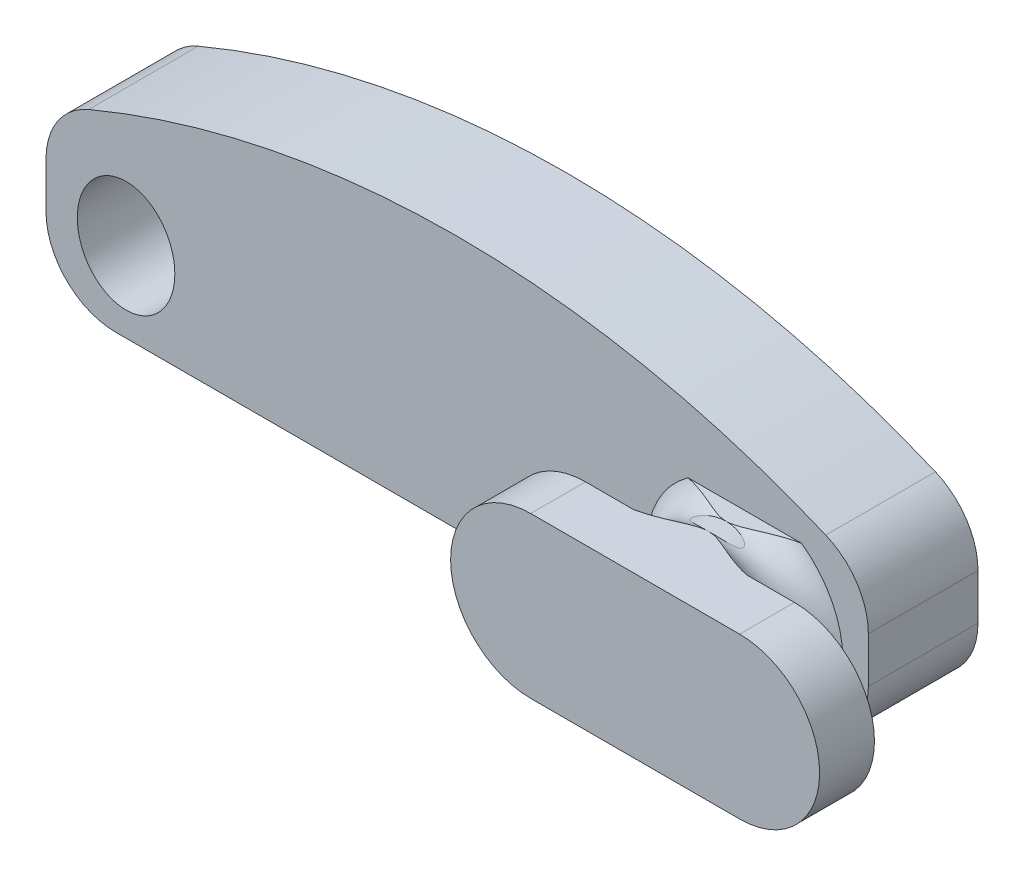
SolidWorks part; units mm, degrees
ref_plane "Front Plane" through (0, 0, 0) normal (0, 0, 1) x (1, 0, 0)
ref_plane "Top Plane" through (0, 0, 0) normal (0, 1, 0) x (1, 0, 0)
ref_plane "Right Plane" through (0, 0, 0) normal (1, 0, 0) x (0, 0, -1)
sketch "Sketch1" plane through (0, 0, 0) normal (0, 0, 1) x (1, 0, 0)
  line L1 (0, 0) -> (-30, 0)
  line L2 (0, 0) -> (0, 5.842)
  line L3 (0, 5.842) -> (-30, 5.842)
  line L4 (-30, 0) -> (-30, 5.842)
  dimension "D1" = 30
  dimension "D2" = 5.842
extrude "Boss-Extrude1" add sketch "Sketch1" along normal blind 4
sketch "Sketch2" plane through (0, 0, 4) normal (0, 0, 1) x (1, 0, 0)
  line L0 (-30, 2.921) -> (0, 2.921) construction
  line L1 (-30, 5.842) -> (-30, 0) construction
  line L2 (0, 0) -> (0, 5.842) construction
  line L3 (-30, 0) -> (0, 0) construction
  line L4 (-1.5875, 5.842) -> (-7.4295, 5.842)
  line L5 (-1.5875, 5.842) -> (-1.5875, 0)
  line L6 (-1.5875, 0) -> (-7.4295, 0)
  line L7 (-7.4295, 5.842) -> (-7.4295, 0)
  line L9 (0, 5.842) -> (-30, 5.842) construction
  ellipse E0 centre (-4.5085, 2.921) end of major axis (-4.5085, 0) minor radius 2.54
  dimension "D1" = 5.08
  dimension "D3" = 1.5875
extrude "Boss-Extrude2" add sketch "Sketch2" along normal blind 2 contours E0
sketch "Sketch3" plane through (0, 0, 6) normal (0, 0, 1) x (1, 0, 0)
  line L0 (-0.6985, 2.921) -> (-8.3185, 2.921) construction
  line L1 (-0.6985, 0) -> (-8.3185, 0)
  line L2 (-0.6985, 5.842) -> (-8.3185, 5.842)
  line L3 (-7.0485, 2.921) -> (-1.9685, 2.921) construction
  line L4 (-4.5085, 5.842) -> (-4.5085, 0) construction
  line L5 (-4.5085, 5.842) -> (-30, 5.842) construction
  arc A1 (-0.6985, 0) -> (-0.6985, 5.842) centre (-0.6985, 2.921) ccw
  arc A2 (-8.3185, 5.842) -> (-8.3185, 0) centre (-8.3185, 2.921) ccw
  ellipse E3 centre (-4.5085, 2.921) end of major axis (-4.5085, 0) minor radius 2.54 construction
  point P2 (-4.5085, 2.921)
  point P28 (-4.5085, 2.921)
  dimension "D2" = 7.62
extrude "Boss-Extrude3" add sketch "Sketch3" along normal blind 2
sketch "Sketch4" plane through (0, 0, 4) normal (0, 0, 1) x (1, 0, 0)
  line L0 (-30, 5.842) -> (-24.158, 0) construction
  line L1 (-30, 0) -> (-4.5085, 0) construction
  line L2 (-30, 0) -> (-24.158, 5.842) construction
  line L3 (-4.5085, 5.842) -> (-30, 5.842) construction
  line L4 (-30, 5.842) -> (-30, 0) construction
  ellipse E0 centre (-27.079, 2.921) end of major axis (-27.079, 4.953) minor radius 1.778
  point P11 (-28.857, 2.921)
  point P17 (0, 0)
  dimension "D1" = 90
  dimension "D2" = 3.556
  dimension "D3" = 4.064
  dimension "D4" = 1.143
extrude "Cut-Extrude1" cut sketch "Sketch4" against normal up to next
ref_axis "Axis1" through (-30, 2.921, 4) along (1, 0, 0)
ref_plane "Plane1" through (0, 2.921, 0) normal (0, -1, 0) x (1, 0, 0)
ref_point "Point1"
ref_axis "Axis2" through (-4.5085, 2.921, 5) along (0, 0, 1)
sketch "Sketch5" plane through (0, 2.921, 0) normal (0, -1, 0) x (1, 0, 0)
  line L1 (-0.6985, 6) -> (2.2225, 6) construction
  line L2 (-0.9296, 6) -> (-3.3465, 6)
  line L3 (-3.3465, 6) -> (-3.3465, 4)
  line L4 (-30, 4) -> (0, 4) construction
  line L5 (-3.3465, 4) -> (-0.9296, 4)
  arc A0 (-0.9296, 4) -> (-0.9296, 6) centre (-0.5764, 5) cw
revolve "Revolve2" add sketch "Sketch5" angle 360 about axis through (-4.5085, 2.921, 5) along (0, 0, 1)
sketch "Sketch6" plane through (0, 0, 8) normal (0, 0, 1) x (1, 0, 0)
  line L0 (-6.5764, 5.842) -> (-30, 5.842) construction
  line L1 (-9.7171, 5.842) -> (0, 5.842)
  line L2 (-9.7171, 5.842) -> (-9.7171, 9.6853)
  line L3 (-9.7171, 9.6853) -> (0, 9.6853)
  line L4 (0, 5.842) -> (0, 9.6853)
  line L5 (-30, 0) -> (-6.5764, 0) construction
  line L6 (-9.7171, 0) -> (0, 0)
  line L7 (-9.7171, 0) -> (-9.7171, -2.7839)
  line L8 (-9.7171, -2.7839) -> (0, -2.7839)
  line L9 (0, 0) -> (0, -2.7839)
extrude "Cut-Extrude2" cut sketch "Sketch6" against normal through all
sketch "Sketch7" plane through (0, 0, 0) normal (0, 0, 1) x (1, 0, 0)
  line L0 (-6.5764, 5.842) -> (-30, 5.842) construction
  line L1 (-30, 5.842) -> (0, 5.842)
  arc A0 (-30, 5.842) -> (0, 5.842) centre (-15, -25.3572) cw
  point P3 (-15, 9.2606)
  dimension "D1" = 3.4186
extrude "Boss-Extrude4" add sketch "Sketch7" along normal up to surface (4 mm away) up to face at (-18.6659, 2.921, 4)
fillet "Fillet1" radius 2.54 2 edges at (0, 0, 2) (-30, 0, 2)
fillet "Fillet2" radius 2.54 2 edges at (0, 5.842, 2) (-30, 5.842, 2)
